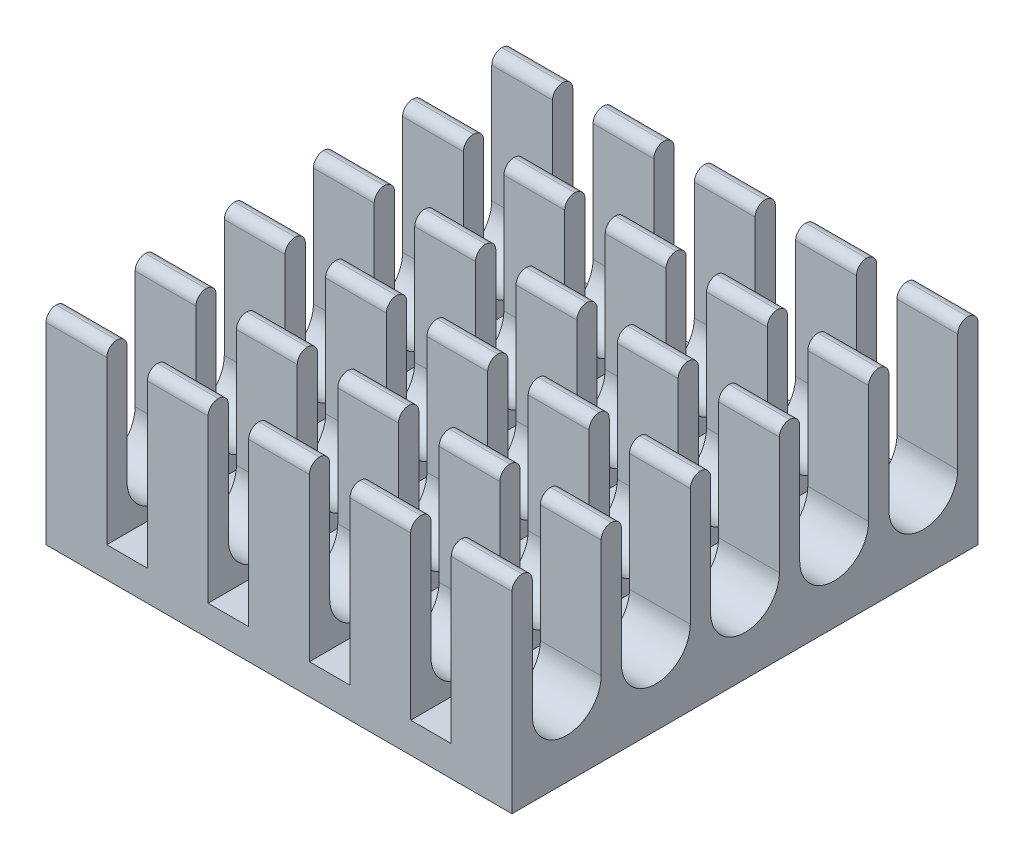
SolidWorks part; units mm, degrees
other "Cámara1"
ref_plane "Alzado" through (0, 0, 0) normal (0, 0, 1) x (1, 0, 0)
ref_plane "Planta" through (0, 0, 0) normal (0, 1, 0) x (1, 0, 0)
ref_plane "Vista lateral" through (0, 0, 0) normal (1, 0, 0) x (0, 0, -1)
sketch "Croquis1" plane through (0, 0, 0) normal (0, 1, 0) x (1, 0, 0)
  line L1 (11.5, 11.5) -> (-11.5, 11.5)
  line L2 (11.5, 11.5) -> (11.5, -11.5)
  line L3 (11.5, -11.5) -> (-11.5, -11.5)
  line L4 (-11.5, 11.5) -> (-11.5, -11.5)
  line L5 (11.5, 11.5) -> (-11.5, -11.5) construction
  line L6 (11.5, -11.5) -> (-11.5, 11.5) construction
  point P0 (0, 0)
  dimension "D1" = 23
  dimension "D2" = 23
extrude "Saliente-Extruir4" add sketch "Croquis1" along normal blind 10 contours L2 L1 L4 L3
sketch "Croquis2" plane through (0, 0, 11.5) normal (0, 0, 1) x (1, 0, 0)
  line L0 (11.5, 10) -> (-11.5, 10) construction
  line L1 (-8.5, 10) -> (-6.5, 10)
  line L2 (-8.5, 10) -> (-8.5, 1.5)
  line L3 (-8.5, 1.5) -> (-6.5, 1.5)
  line L4 (-6.5, 10) -> (-6.5, 1.5)
  line L5 (-11.5, 10) -> (-11.5, 0) construction
  line L6 (11.5, 0) -> (-11.5, 0) construction
  line L7 (-3.5, 10) -> (-3.5, 1.5)
  line L8 (-3.5, 10) -> (-1.5, 10)
  line L9 (-1.5, 10) -> (-1.5, 1.5)
  line L10 (-3.5, 1.5) -> (-1.5, 1.5)
  line L11 (1.5, 10) -> (1.5, 1.5)
  line L12 (1.5, 10) -> (3.5, 10)
  line L13 (3.5, 10) -> (3.5, 1.5)
  line L14 (1.5, 1.5) -> (3.5, 1.5)
  line L15 (6.5, 10) -> (6.5, 1.5)
  line L16 (6.5, 10) -> (8.5, 10)
  line L17 (8.5, 10) -> (8.5, 1.5)
  line L18 (6.5, 1.5) -> (8.5, 1.5)
  line L19 (-8.5, 10) -> (-3.5, 10) construction
  dimension "D1" = 2
  dimension "D2" = 3
  dimension "D3" = 1.5
  dimension "D5" = 5
  dimension "D4" = 4
extrude "Cortar-Extruir2" cut sketch "Croquis2" against normal through all contours L4 L6 L2 L3 | L11 L14 L13 L6 | L15 L18 L17 L6 | L7 L10 L9 L8 region at (-7.5, 5.75, 11.5) region at (2.5, 5.75, 11.5) region at (7.5, 5.75, 11.5)
sketch "Croquis3" plane through (11.5, 0, 0) normal (1, 0, 0) x (0, 0, -1)
  line L0 (11.5, 10) -> (-11.5, 10) construction
  line L1 (-10.5, 10) -> (-7.1, 10)
  line L2 (-10.5, 10) -> (-10.5, 3.7)
  line L4 (-7.1, 10) -> (-7.1, 3.7)
  line L5 (-11.5, 10) -> (-11.5, 0) construction
  line L7 (-6.1, 10) -> (-6.1, 3.7)
  line L8 (-6.1, 10) -> (-2.7, 10)
  line L9 (-2.7, 10) -> (-2.7, 3.7)
  line L11 (-1.7, 10) -> (-1.7, 3.7)
  line L12 (-1.7, 10) -> (1.7, 10)
  line L13 (1.7, 10) -> (1.7, 3.7)
  line L15 (2.7, 10) -> (2.7, 3.7)
  line L16 (2.7, 10) -> (6.1, 10)
  line L17 (6.1, 10) -> (6.1, 3.7)
  line L19 (7.1, 10) -> (7.1, 3.7)
  line L20 (7.1, 10) -> (10.5, 10)
  line L21 (10.5, 10) -> (10.5, 3.7)
  line L23 (-10.5, 10) -> (-6.1, 10) construction
  arc A1 (-10.5, 3.7) -> (-7.1, 3.7) centre (-8.8, 3.7) ccw
  arc A2 (-6.1, 3.7) -> (-2.7, 3.7) centre (-4.4, 3.7) ccw
  arc A3 (-1.7, 3.7) -> (1.7, 3.7) centre (0, 3.7) ccw
  arc A4 (2.7, 3.7) -> (6.1, 3.7) centre (4.4, 3.7) ccw
  arc A5 (7.1, 3.7) -> (10.5, 3.7) centre (8.8, 3.7) ccw
  point P1 (-8.8, 2)
  dimension "D1" = 1
  dimension "D2" = 8
  dimension "D3" = 3.4
  dimension "D5" = 4.4
  dimension "D6" = 5
  dimension "D4" = 5
extrude "Cortar-Extruir6" cut sketch "Croquis3" against normal through all
fillet "Redondeo14" radius 0.5 58 edges at (-5, 10, -2.7) (-5, 10, -1.7) (-10, 10, -2.7) (-10, 10, -1.7) (-10, 10, 1.7) (-10, 10, 2.7) (-5, 10, 1.7) (-5, 10, 2.7) (-5, 10, 6.1) (-5, 10, 7.1) (-5, 10, 10.5) (-5, 10, 11.5) (-10, 10, 6.1) (-10, 10, 7.1) (-10, 10, 10.5) (-10, 10, 11.5) (0, 10, -2.7) (0, 10, -1.7) (0, 10, 1.7) (0, 10, 2.7) (0, 10, 6.1) (0, 10, 7.1) (0, 10, 10.5) (0, 10, 11.5) (5, 10, 11.5) (5, 10, 10.5) (5, 10, 7.1) (5, 10, 6.1) (5, 10, 2.7) (5, 10, 1.7) (5, 10, -1.7) (5, 10, -2.7) (5, 10, -6.1) (5, 10, -7.1) (0, 10, -6.1) (0, 10, -7.1) (-5, 10, -6.1) (-5, 10, -7.1) (-10, 10, -6.1) (-10, 10, -7.1) (-10, 10, -10.5) (-10, 10, -11.5) (-5, 10, -10.5) (-5, 10, -11.5) (0, 10, -11.5) (5, 10, -11.5) (10, 10, 10.5) (10, 10, 11.5) (10, 10, 7.1) (10, 10, 6.1) (10, 10, 2.7) (10, 10, 1.7) (10, 10, -1.7) (10, 10, -2.7) (10, 10, -7.1) (10, 10, -6.1) (10, 10, -10.5) (10, 10, -11.5)
fillet "Redondeo15" radius 0.5 2 edges at (5, 10, -10.5) (0, 10, -10.5)
